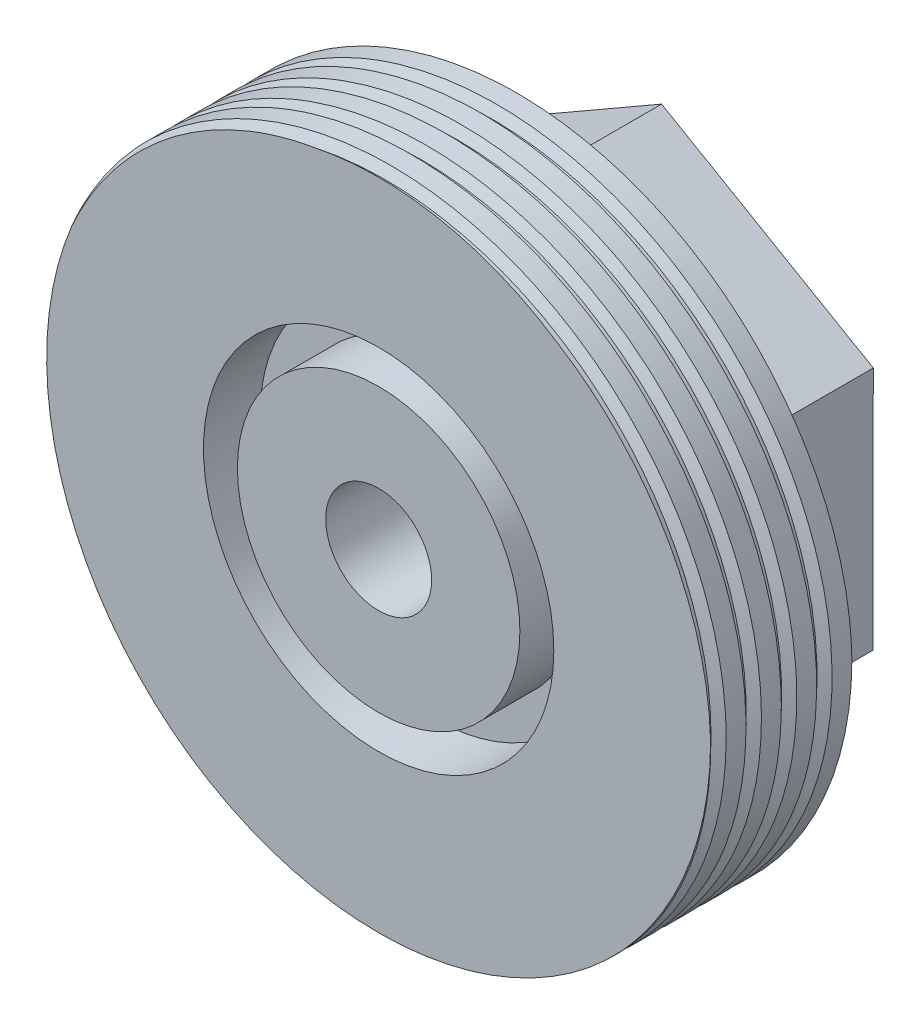
SolidWorks part; units mm, degrees
ref_plane "Front Plane" through (0, 0, 0) normal (0, 0, 1) x (1, 0, 0)
ref_plane "Top Plane" through (0, 0, 0) normal (0, 1, 0) x (1, 0, 0)
ref_plane "Right Plane" through (0, 0, 0) normal (1, 0, 0) x (0, 0, -1)
sketch "Sketch3" plane through (0, 0, 0) normal (0, 0, 1) x (1, 0, 0)
  circle A3 centre (8.3476, 27.7238) radius 14.9225
  dimension "D1" = 29.845
extrude "Boss-Extrude1" add sketch "Sketch3" against normal blind 12.7 contours A3 region at (8.3476, 27.7238, 0)
sketch "Sketch11" plane through (0, 0, 0) normal (0, 0, 1) x (1, 0, 0)
  circle A0 centre (8.3476, 27.7238) radius 2.3813
  dimension "D1" = 4.7625
extrude "Cut-Extrude3" cut sketch "Sketch11" against normal blind 6.35
sketch "Sketch12" plane through (0, 0, 0) normal (0, 0, 1) x (1, 0, 0)
  circle A0 centre (8.3476, 27.7238) radius 6.35
  circle A1 centre (8.3476, 27.7238) radius 7.874
  dimension "D1" = 15.748
  dimension "D2" = 1.524
extrude "Cut-Extrude4" cut sketch "Sketch12" against normal blind 2.54
thread "Thread1" pitch 0.7937 method cut profile "Thread Profile1" start angle 0, offset 0.7937, length 7.62, pitch 1.5875, diameter 29.845
ref_plane "Plane1" through (-6.5749, 27.7238, 0.7937) normal (0, -1, 0) x (-1, 0, 0)
sketch "Thread Profile1" plane through (-6.5749, 27.7238, 0.7937) normal (0, -1, 0) x (-1, 0, 0)
  line L0 (0, 0) -> (0, 0.7937) construction
  line L11 (0, 0) -> (0, 0.6945)
  line L12 (0, 0.6945) -> (-0.4296, 0.4465)
  line L13 (-0.4296, 0.4465) -> (-0.4296, 0.248)
  line L15 (-0.4296, 0.248) -> (0, 0)
  line L17 (-0.4296, 0.3473) -> (0, 0.3473) construction
  point P2 (0, 0)
  dimension "Pitch" = 0.7937
  dimension "Profile_Angle" = 60
  dimension "Profile_Land" = 0.1984
  dimension "Profile_Height" = 0.4296
sketch "Sketch13" plane through (0, 0, -12.7) normal (0, 0, -1) x (-1, 0, 0)
  circle A0 centre (-8.3476, 27.7238) radius 2.3813
extrude "Cut-Extrude5" cut sketch "Sketch13" against normal blind 6.35
sketch "Sketch14" plane through (0, 0, -12.7) normal (0, 0, -1) x (-1, 0, 0)
  line L1 (1.1867, 22.2406) -> (1.1681, 33.2391)
  line L2 (1.1681, 33.2391) -> (-8.3661, 38.7223)
  line L3 (-8.3661, 38.7223) -> (-17.8818, 33.207)
  line L4 (-17.8818, 33.207) -> (-17.8633, 22.2085)
  line L5 (-17.8633, 22.2085) -> (-8.3291, 16.7253)
  line L6 (-8.3291, 16.7253) -> (1.1867, 22.2406)
  circle A0 centre (-8.3476, 27.7238) radius 9.525 construction
  circle A3 centre (-8.3476, 27.7238) radius 14.9225
  circle A4 centre (-8.3476, 27.7238) radius 14.9225
  dimension "D2" = 0
  dimension "D1" = 19.05
extrude "Cut-Extrude6" cut sketch "Sketch14" against normal blind 6.35
ref_point "Point1"
